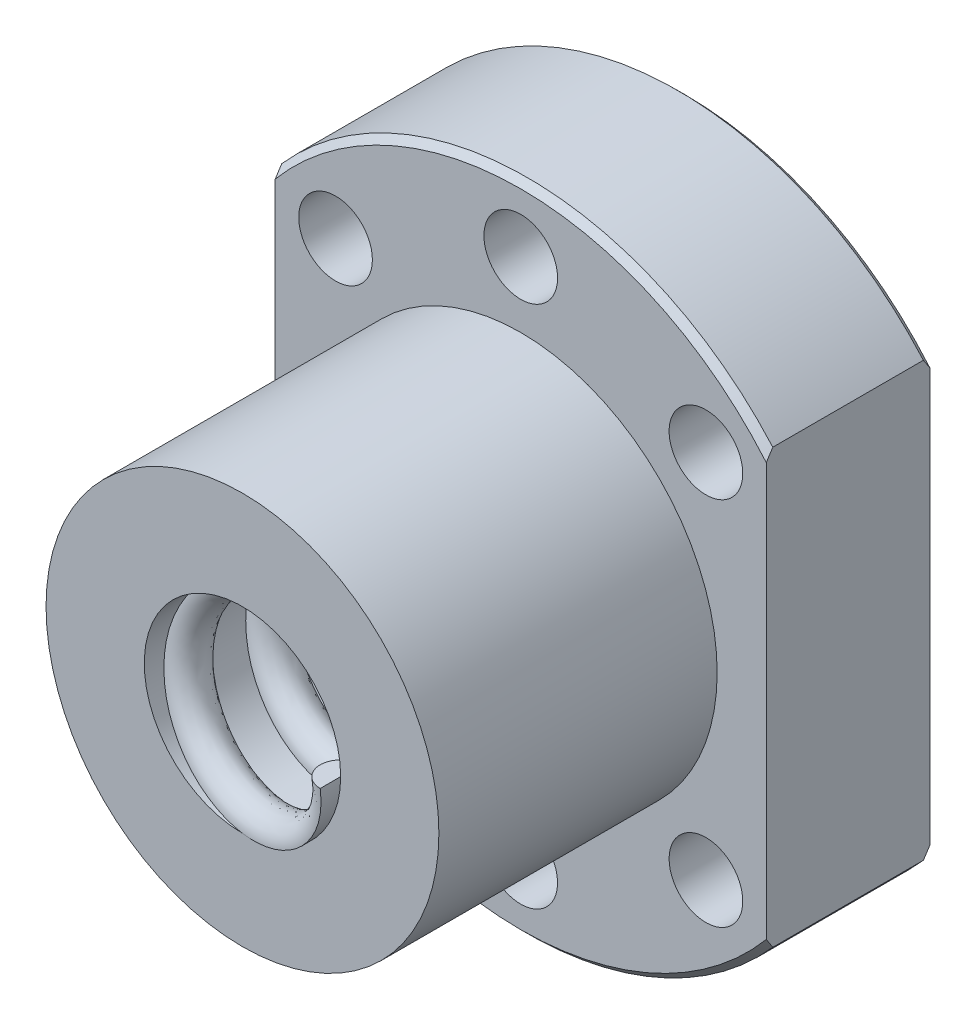
SolidWorks part; units mm, degrees
material "AISI 321 Acero inoxidable recocido (SS)"
ref_plane "Alzado" through (0, 0, 0) normal (0, 0, 1) x (1, 0, 0)
ref_plane "Planta" through (0, 0, 0) normal (0, 1, 0) x (1, 0, 0)
ref_plane "Vista lateral" through (0, 0, 0) normal (1, 0, 0) x (0, 0, -1)
sketch "Croquis1" plane through (0, 0, 0) normal (0, 0, 1) x (1, 0, 0)
  line L0 (-15, -13.2288) -> (15, -13.2288) construction
  line L1 (-15, -13.2288) -> (-15, 13.2288)
  line L2 (15, -13.2288) -> (15, 13.2288)
  line L3 (0, 0) -> (0, 10.2389) construction
  line L4 (0, 0) -> (-11.3137, 11.3137) construction
  line L5 (0, 0) -> (9.9897, 0) construction
  arc A0 (-15, -13.2288) -> (15, -13.2288) centre (0, 0) ccw
  arc A1 (15, 13.2288) -> (-15, 13.2288) centre (0, 0) ccw
  circle A2 centre (0, 0) radius 16 construction
  circle A3 centre (-11.3137, 11.3137) radius 2.25
  circle A4 centre (0, 16) radius 2.25
  circle A5 centre (11.3137, 11.3137) radius 2.25
  circle A6 centre (11.3137, -11.3137) radius 2.25
  circle A7 centre (0, -16) radius 2.25
  circle A8 centre (-11.3137, -11.3137) radius 2.25
  circle A11 centre (0, 0) radius 6
  point P18 (0, 0)
  point P19 (0, 0)
  dimension "D1" = 40
  dimension "D3" = 32
  dimension "D5" = 4.5
  dimension "D7" = 12
  dimension "D2" = 30
  dimension "D4" = 45
  dimension "D6" = 3
extrude "Saliente-Extruir1" add sketch "Croquis1" along normal blind 10
sketch "Croquis2" plane through (0, 0, 10) normal (0, 0, 1) x (1, 0, 0)
  circle A0 centre (0, 0) radius 12
  circle A1 centre (0, 0) radius 6
  dimension "D1" = 24
extrude "Saliente-Extruir2" add sketch "Croquis2" along normal blind 17
chamfer "Chaflán1" distance 0.4 angle 45 4 edges at (0, -20, 0) (0, -20, 10) (0, 20, 0) (0, 20, 10)
ref_plane "Plano1" through (0, 12, 0) normal (0, 1, 0) x (1, 0, 0)
sketch "Croquis7" plane through (0, 0, 27) normal (0, 0, 1) x (1, 0, 0)
  circle A0 centre (0, 0) radius 6 construction
  circle A1 centre (0, 0) radius 6
curve "Hélice/Espiral1" pitch 5 height 23 radius 6 centre (0, 0, 27) axis (0, 0, -1) start towards (1, 0, 0)
sketch "Croquis9" plane through (0, 0, 0) normal (0, 1, 0) x (1, 0, 0)
  line L0 (6, -25.75) -> (6, -28.25)
  arc A0 (6, -25.75) -> (6, -28.25) centre (6, -27) ccw
  dimension "D1" = 2.5
sweep "Barrer2" add profiles "Croquis9" path "Hélice/Espiral1"
sketch "Croquis3" [suppressed] plane through (0, 12, 0) normal (0, 1, 0) x (1, 0, 0)
  line L0 (-12, -27) -> (12, -27) construction
  circle A0 centre (0, -18.5) radius 1.5
  dimension "D1" = 8.5
  dimension "D2" = 3
extrude "Cortar-Extruir1" [suppressed] cut sketch "Croquis3" against normal blind 1.5
sketch "Croquis4" [suppressed] plane through (0, 0, 0) normal (0, 0, -1) x (-1, 0, 0)
  circle A0 centre (0, 0) radius 12
  dimension "D1" = 24
extrude "Cortar-Extruir2" [suppressed] cut sketch "Croquis4" against normal blind 4
sketch "Croquis5" [suppressed] plane through (0, 0, 27) normal (0, 0, 1) x (1, 0, 0)
  circle A0 centre (0, 9.35) radius 0.65
  circle A1 centre (8.0973, -4.675) radius 0.65
  circle A2 centre (-8.0973, -4.675) radius 0.65
  point P10 (0, 0)
  dimension "D1" = 1.3
  dimension "D2" = 9.35
  dimension "D3" = 3
extrude "Cortar-Extruir3" [suppressed] cut sketch "Croquis5" against normal through all
sketch "Croquis10" [suppressed] plane through (15, 0, 0) normal (1, 0, 0) x (0, 0, -1)
  line L1 (-27, -12) -> (-32.805, -12)
  line L2 (-27, -12) -> (-27, 8.5097)
  line L3 (-27, 8.5097) -> (-32.805, 8.5097)
  line L4 (-32.805, -12) -> (-32.805, 8.5097)
extrude "Cortar-Extruir4" [suppressed] cut sketch "Croquis10" against normal through all
